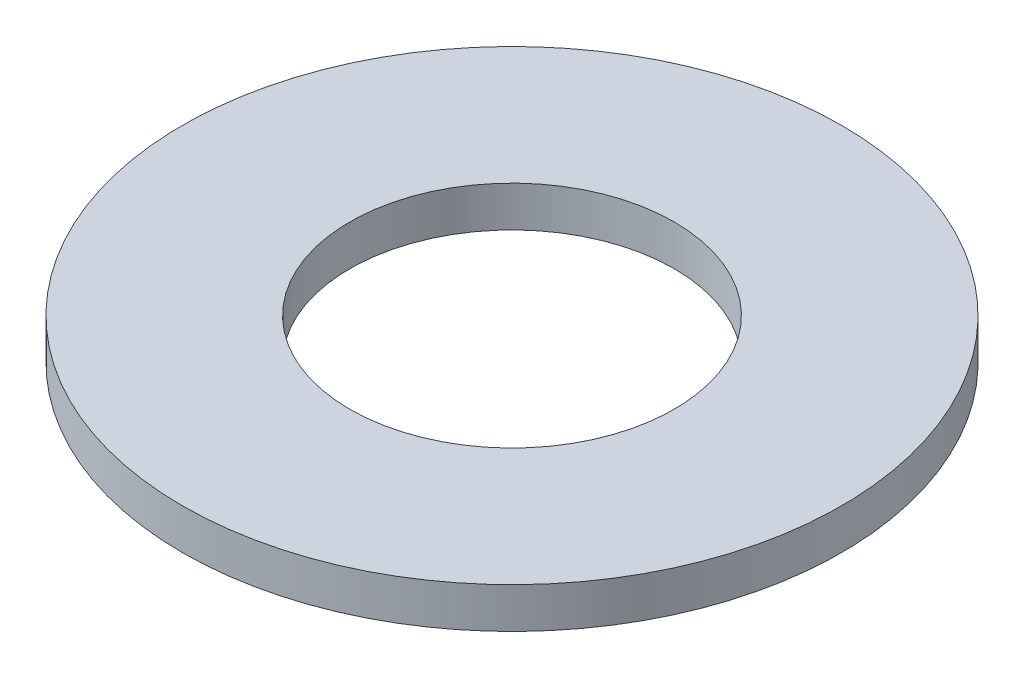
SolidWorks part; units mm, degrees
material "Alum Plate"
ref_plane "Front Plane" through (0, 0, 0) normal (0, 0, 1) x (1, 0, 0)
ref_plane "Top Plane" through (0, 0, 0) normal (0, 1, 0) x (1, 0, 0)
ref_plane "Right Plane" through (0, 0, 0) normal (1, 0, 0) x (0, 0, -1)
other "Bounding Box"
ref_plane "Default Plane" through (0, 2.286, 19.05) normal (0, -1, 0) x (-1, 0, 0)
sketch "Sketch1" plane through (0, 0, 0) normal (0, 1, 0) x (1, 0, 0)
  circle A0 centre (0, 0) radius 4.064
  circle A1 centre (0, 0) radius 8.255
  dimension "D1" = 8.128
  dimension "D2" = 16.51
extrude "Boss-Extrude1" add sketch "Sketch1" along normal mid plane 1.016
equation "\"Unit Measure\"= \"BoundingVolume\" / \"Thickness\"'in^2"
